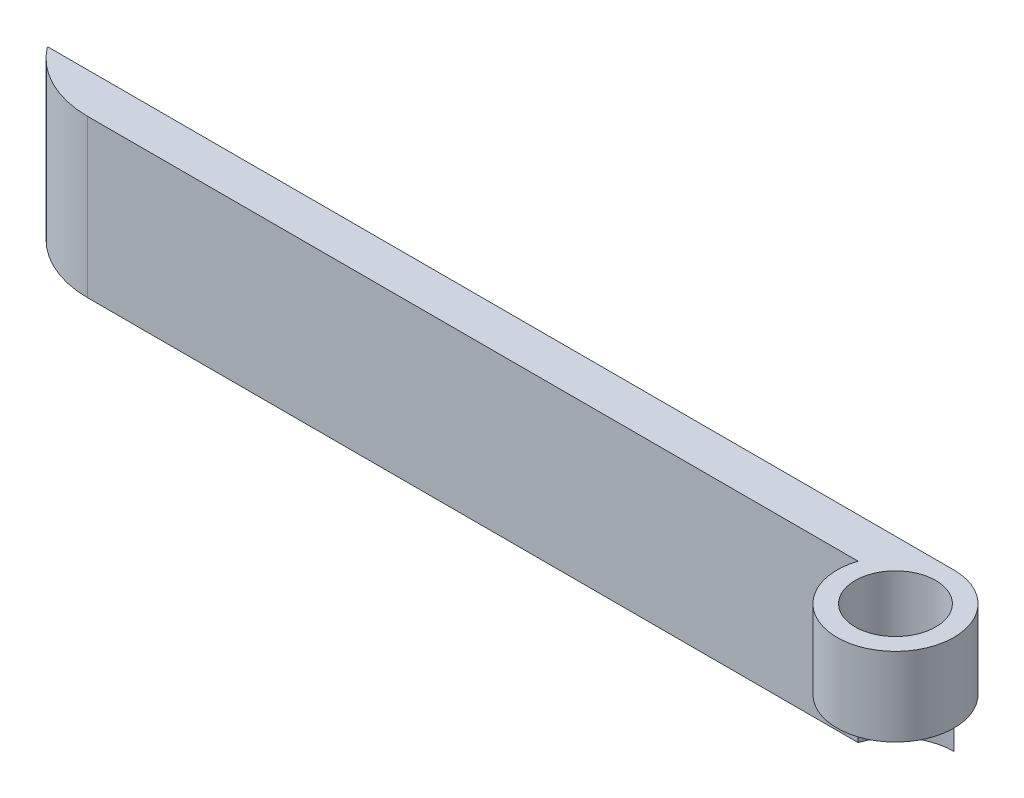
SolidWorks part; units mm, degrees
ref_plane "Alzado" through (0, 0, 0) normal (0, 0, 1) x (1, 0, 0)
ref_plane "Planta" through (0, 0, 0) normal (0, 1, 0) x (1, 0, 0)
ref_plane "Vista lateral" through (0, 0, 0) normal (1, 0, 0) x (0, 0, -1)
sketch "Croquis1" plane through (0, 0, 0) normal (0, 1, 0) x (1, 0, 0)
  circle A0 centre (0, 0) radius 2.9
  circle A1 centre (0, 0) radius 2
  dimension "D1" = 5.8
  dimension "D2" = 4
extrude "Saliente-Extruir1" add sketch "Croquis1" along normal blind 3.9
sketch "Croquis2" plane through (0, 0, 0) normal (0, -1, 0) x (1, 0, 0)
  line L0 (0, 3.7949) -> (0, 2.9) construction
  line L1 (0, -2.9) -> (-45, -2.9)
  line L2 (-45, -2.9) -> (-45, -0.9)
  line L3 (-45, -0.9) -> (-2.7568, -0.9)
  line L5 (0, -2.9) -> (0, -4.2431) construction
  circle A0 centre (0, 0) radius 2.9
  circle M5 centre (0, 0) radius 2.9
  dimension "D2" = 5.8
  dimension "D1" = 2
  dimension "D3" = 45
extrude "Saliente-Extruir2" add sketch "Croquis2" along normal blind 3.9 and the other way blind 3.9 contours L3 L2 L1 M5 region at (-23.5049, 0, -1.908)
fillet "Redondeo1" radius 5 1 edges at (-45, 0, -0.9)
